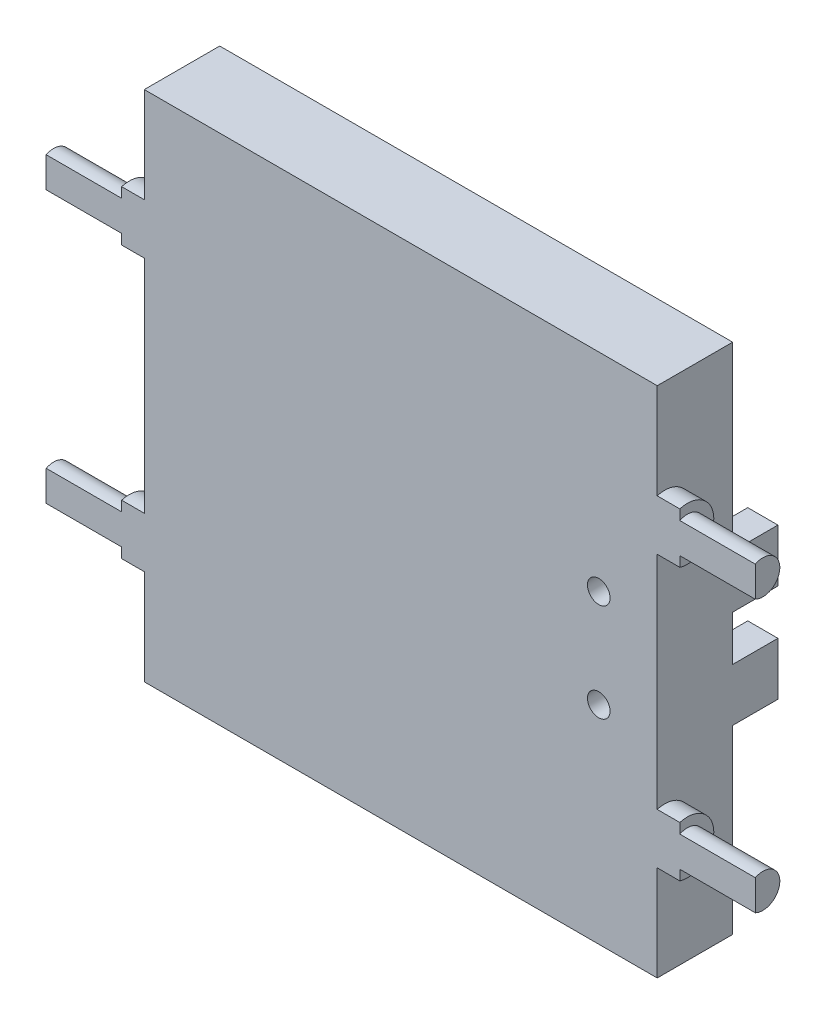
SolidWorks part; units mm, degrees
ref_plane "Front Plane" through (0, 0, 0) normal (0, 0, 1) x (1, 0, 0)
ref_plane "Top Plane" through (0, 0, 0) normal (0, 1, 0) x (1, 0, 0)
ref_plane "Right Plane" through (0, 0, 0) normal (1, 0, 0) x (0, 0, -1)
sketch "Sketch1" plane through (0, 0, 0) normal (0, 0, 1) x (1, 0, 0)
  line L1 (0, 0) -> (-68, 0)
  line L2 (0, 0) -> (0, -68)
  line L3 (0, -68) -> (-68, -68)
  line L4 (-68, 0) -> (-68, -68)
  dimension "D1" = 68
  dimension "D2" = 68
extrude "Boss-Extrude1" add sketch "Sketch1" along normal blind 10
sketch "Sketch2" plane through (-68, 0, 0) normal (-1, 0, 0) x (0, 0, 1)
  line L1 (10, 0) -> (0, 0) construction
  line L2 (10, -68) -> (0, -68) construction
  line L3 (10, 0) -> (10, -68) construction
  line L4 (10, 0) -> (10, -68)
  circle A0 centre (9, -52) radius 3.5
  circle A1 centre (9, -16) radius 3.5
  dimension "D1" = 7
  dimension "D2" = 7
  dimension "D3" = 1
  dimension "D4" = 0
  dimension "D5" = 16
  dimension "D6" = 16
extrude "Boss-Extrude2" add sketch "Sketch2" along normal blind 3 contours L4 A1 | L4 A0 region at (-68, -52, 8.0379) region at (-68, -16, 8.0379)
sketch "Sketch3" plane through (-71, 0, 0) normal (-1, 0, 0) x (0, 0, 1)
  line L0 (10, -55.3541) -> (10, -12.6459)
  circle A0 centre (9, -52) radius 2.25
  circle A1 centre (9, -16) radius 2.25
  dimension "D1" = 4.5
  dimension "D2" = 4.5
extrude "Boss-Extrude3" add sketch "Sketch3" along normal blind 10 contours L0 A0 | L0 A1 region at (-71, -52, 8.5562) region at (-71, -16, 8.5562)
sketch "Sketch4" plane through (0, 0, 0) normal (1, 0, 0) x (0, 0, -1)
  line L0 (-10, 0) -> (0, 0) construction
  line L1 (-10, -68) -> (0, -68) construction
  line L2 (-10, 0) -> (-10, -68)
  circle A0 centre (-9, -16) radius 3.5
  circle A1 centre (-9, -52) radius 3.5
  dimension "D1" = 16
  dimension "D2" = 16
  dimension "D3" = 7
  dimension "D4" = 7
  dimension "D5" = 1
  dimension "D6" = 0
extrude "Boss-Extrude4" add sketch "Sketch4" along normal blind 3 contours L2 A0 | L2 A1 region at (0, -16, 8.0379) region at (0, -52, 8.0379)
sketch "Sketch5" plane through (3, 0, 0) normal (1, 0, 0) x (0, 0, -1)
  line L0 (-10, -12.6459) -> (-10, -55.3541)
  circle A0 centre (-9, -16) radius 2.25
  circle A1 centre (-9, -52) radius 2.25
  dimension "D1" = 4.5
  dimension "D2" = 4.5
extrude "Boss-Extrude5" add sketch "Sketch5" along normal blind 10 contours L0 A0 | L0 A1 region at (3, -16, 8.5562) region at (3, -52, 8.5562)
sketch "Sketch6" plane through (0, 0, 0) normal (0, 0, -1) x (-1, 0, 0)
  line L0 (0, -34) -> (68, -34) construction
  line L1 (55.25, -12.75) -> (12.75, -12.75)
  line L2 (55.25, -12.75) -> (55.25, -55.25)
  line L3 (55.25, -55.25) -> (12.75, -55.25)
  line L4 (12.75, -12.75) -> (12.75, -55.25)
  line L5 (0, -68) -> (0, 0) construction
  line L6 (68, 0) -> (68, -68) construction
  line L7 (34, 0) -> (34, -68) construction
  line L8 (0, 0) -> (68, 0) construction
  line L9 (68, -68) -> (0, -68) construction
  point P16 (12.75, -34)
  point P17 (34, -55.25)
  dimension "D1" = 42.5
  dimension "D2" = 42.5
  dimension "D3" = 0
  dimension "D4" = 0
extrude "Cut-Extrude1" cut sketch "Sketch6" against normal blind 3
sketch "Sketch8" plane through (0, 0, 0) normal (0, 0, -1) x (-1, 0, 0)
  line L0 (55.25, -12.75) -> (12.75, -12.75) construction
  line L1 (12.75, -55.25) -> (55.25, -55.25) construction
  line L2 (12.75, -12.75) -> (12.75, -55.25) construction
  line L3 (34, 0) -> (34, -108.8236) construction
  line L4 (0, 0) -> (68, 0) construction
  circle A0 centre (4.75, -17.75) radius 1.5
  circle A1 centre (4.75, -50.25) radius 1.5
  circle A2 centre (63.25, -50.25) radius 1.5
  circle A3 centre (63.25, -17.75) radius 1.5
  dimension "D1" = 5
  dimension "D2" = 5
  dimension "D3" = 3
  dimension "D4" = 3
  dimension "D5" = 8
  dimension "D6" = 8
extrude "Cut-Extrude2" cut sketch "Sketch8" against normal blind 5
sketch "Sketch9" plane through (0, 0, 0) normal (0, 0, -1) x (-1, 0, 0)
  line L1 (0, -24) -> (4, -24)
  line L2 (0, -24) -> (0, -31)
  line L3 (0, -31) -> (4, -31)
  line L4 (4, -24) -> (4, -31)
  line L5 (0, -68) -> (0, 0) construction
  line L6 (0, -34) -> (68, -34) construction
  line L7 (68, 0) -> (68, -68) construction
  line L8 (0, -37) -> (4, -37)
  line L9 (4, -44) -> (4, -37)
  line L10 (0, -44) -> (4, -44)
  line L11 (0, -44) -> (0, -37)
  point P6 (0, -34)
  dimension "D1" = 4
  dimension "D2" = 7
  dimension "D3" = 0
  dimension "D4" = 3
extrude "Boss-Extrude6" add sketch "Sketch9" along normal blind 6
sketch "Sketch10" plane through (0, 0, 0) normal (0, 0, -1) x (-1, 0, 0)
  line L0 (0, -34) -> (23.3312, -34) construction
  line L1 (0, -37) -> (0, -31) construction
  line L2 (12.75, -12.75) -> (12.75, -55.25) construction
  line L3 (4, -31) -> (4, -24) construction
  circle A0 centre (7.75, -27.5) radius 1.5
  circle A1 centre (7.75, -40.5) radius 1.5
  point P10 (4, -27.5)
  point P11 (0, 0)
  dimension "D1" = 3
  dimension "D2" = 5
  dimension "D3" = 0
extrude "Cut-Extrude3" cut sketch "Sketch10" against normal blind 10
